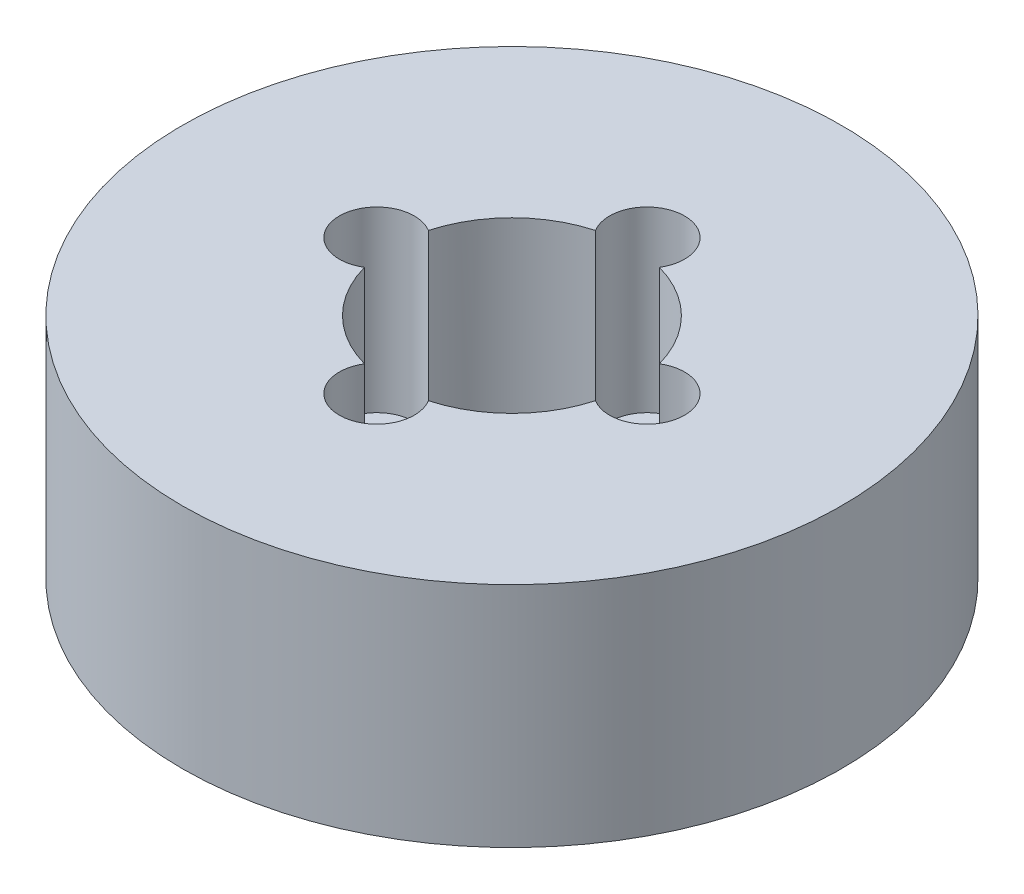
SolidWorks part; units mm, degrees
ref_plane "Front Plane" through (0, 0, 0) normal (0, 0, 1) x (1, 0, 0)
ref_plane "Top Plane" through (0, 0, 0) normal (0, 1, 0) x (1, 0, 0)
ref_plane "Right Plane" through (0, 0, 0) normal (1, 0, 0) x (0, 0, -1)
sketch "Sketch1" plane through (0, 0, 0) normal (0, 1, 0) x (1, 0, 0)
  circle A0 centre (0, 0) radius 27.5
  dimension "FLANGE_OD" = 55
extrude "Boss-Extrude1" add sketch "Sketch1" along normal blind 19
sketch "Sketch2" plane through (0, 0, 0) normal (0, 1, 0) x (1, 0, 0)
  circle A0 centre (0, 0) radius 10
  dimension "BORE_D" = 20
extrude "Cut-Extrude1" cut sketch "Sketch2" along normal through all
sketch "Sketch3" plane through (0, 19, 0) normal (0, 1, 0) x (1, 0, 0)
  circle A0 centre (0, 0) radius 11.2743 construction
  circle A1 centre (-11.2743, 0) radius 3.1296
  dimension "BOLT_D" = 6.2592
  dimension "BOLT_PCD" = 22.5485
extrude "Cut-Extrude2" cut sketch "Sketch3" against normal blind 14.866
pattern_circular "CirPattern1" count 4 over 360 about axis through (0, 0, 0) along (0, 1, 0) of "Cut-Extrude2"
